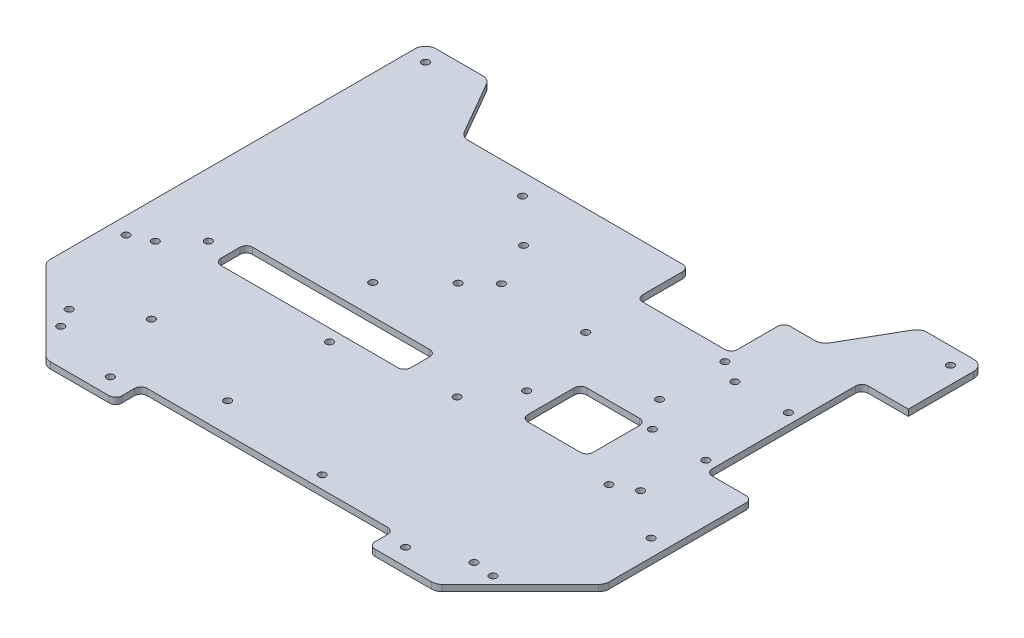
SolidWorks part; units mm, degrees
material "Acier non allié"
ref_plane "Front" through (0, 0, 0) normal (0, 0, 1) x (1, 0, 0)
ref_plane "Top" through (0, 0, 0) normal (0, 1, 0) x (1, 0, 0)
ref_plane "Right" through (0, 0, 0) normal (1, 0, 0) x (0, 0, -1)
sketch "Esquisse1" plane through (0, 0, 0) normal (0, 1, 0) x (1, 0, 0)
  line L0 (0, 0) -> (0, 190) construction
  line L1 (-92.5, 0) -> (92.5, 0)
  line L2 (92.5, 0) -> (132.5, 40)
  line L3 (132.5, 40) -> (132.5, 220)
  line L4 (132.5, 220) -> (102.5, 220)
  line L5 (102.5, 220) -> (85.1795, 190)
  line L6 (85.1795, 190) -> (-85.1795, 190)
  line L7 (-102.5, 220) -> (-85.1795, 190)
  line L8 (-132.5, 220) -> (-102.5, 220)
  line L9 (-132.5, 40) -> (-132.5, 220)
  line L10 (-92.5, 0) -> (-132.5, 40)
  dimension "D1" = 132.5
  dimension "D2" = 220
  dimension "D3" = 60
  dimension "D4" = 30
  dimension "D5" = 40
  dimension "D6" = 40
  dimension "D7" = 30
extrude "Boss.-Extru.1" add sketch "Esquisse1" along normal blind 3
fillet "Congé1" radius 5 10 edges at (92.5, 1.5, 0) (132.5, 1.5, -40) (132.5, 1.5, -220) (102.5, 1.5, -220) (85.1795, 1.5, -190) (-85.1795, 1.5, -190) (-102.5, 1.5, -220) (-132.5, 1.5, -220) (-92.5, 1.5, 0) (-132.5, 1.5, -40)
sketch "Esquisse2" plane through (0, 3, 0) normal (0, 1, 0) x (1, 0, 0)
  line L0 (0, 0) -> (0, 294.1173) construction
  line L2 (-90.4289, 0) -> (90.4289, 0) construction
  circle A0 centre (70, 8) radius 1
  circle A1 centre (124.5, 70) radius 1
  circle A2 centre (124.5, 212) radius 1
  circle A3 centre (-124.5, 212) radius 1
  circle A4 centre (-124.5, 70) radius 1
  circle A5 centre (-70, 8) radius 1
  dimension "D2" = 2
  dimension "D6" = 2
  dimension "D9" = 2
  dimension "D1" = 70
  dimension "D3" = 8
  dimension "D4" = 124.5
  dimension "D5" = 70
  dimension "D7" = 124.5
  dimension "D8" = 212
extrude "Enlèv. mat.-Extru.1" cut sketch "Esquisse2" against normal blind 3
hole_wizard "Dégagement M31" positions "Esquisse3" profile "Esquisse4" hole size "M3" standard "ISO" end condition through all
sketch "Esquisse3" plane through (0, 3, 0) normal (0, 1, 0) x (1, 0, 0)
  point P0 (70, 8)
  point P3 (-70, 8)
  point P6 (-124.5, 70)
  point P9 (-124.5, 212)
  point P12 (124.5, 212)
  point P15 (124.5, 70)
sketch "Esquisse4" plane through (70, 3, -8) normal (1, 0, 0) x (0, 0, 1)
  line L0 (0, 0) -> (0, 3)
  line L1 (0, 3) -> (1.7, 3)
  line L2 (1.7, 3) -> (1.7, 0)
  line L5 (1.7, 0) -> (0, 0)
  line L11 (0, -6.35) -> (0, 107.95) construction
  dimension "Diamètre du perçage jusqu'au prochain" = 3.4
  dimension "Profondeur du perçage jusqu'au prochain" = 3
sketch "Esquisse5" plane through (0, 3, 0) normal (0, 1, 0) x (1, 0, 0)
  line L0 (82.2927, 190) -> (-82.2927, 190) construction
  line L1 (67.5, 190) -> (22.5, 190)
  line L2 (67.5, 190) -> (67.5, 165)
  line L3 (67.5, 165) -> (22.5, 165)
  line L4 (22.5, 190) -> (22.5, 165)
  line L5 (132.5, 42.0711) -> (132.5, 215) construction
  line L6 (132.5, 184) -> (110.5, 184)
  line L7 (132.5, 184) -> (132.5, 110)
  line L8 (132.5, 110) -> (110.5, 110)
  line L9 (110.5, 184) -> (110.5, 110)
  line L10 (127.5, 220) -> (105.3868, 220) construction
  dimension "D1" = 25
  dimension "D2" = 65
  dimension "D3" = 110
  dimension "D4" = 36
  dimension "D5" = 110
  dimension "D6" = 22
extrude "Enlèv. mat.-Extru.2" cut sketch "Esquisse5" against normal through all
fillet "Congé2" radius 3 7 edges at (132.5, 1.5, -110) (110.5, 1.5, -110) (110.5, 1.5, -184) (67.5, 1.5, -190) (67.5, 1.5, -165) (22.5, 1.5, -165) (22.5, 1.5, -190)
sketch "Esquisse6" plane through (0, 3, 0) normal (0, 1, 0) x (1, 0, 0)
  line L0 (110.5, 144.5) -> (-167.6757, 144.5) construction
  line L1 (110.5, 181) -> (110.5, 113) construction
  line L2 (-90.4289, 0) -> (90.4289, 0) construction
  line L3 (110.5, 181) -> (110.5, 113) construction
  circle A0 centre (69.5, 160) radius 1
  circle A1 centre (-26, 160) radius 1
  circle A2 centre (-46.5, 180) radius 1
  circle A3 centre (69.5, 129) radius 1
  circle A4 centre (-26, 129) radius 1
  circle A5 centre (-46.5, 109) radius 1
  dimension "D4" = 2
  dimension "D6" = 2
  dimension "D10" = 2
  dimension "D1" = 144.5
  dimension "D2" = 41
  dimension "D3" = 15.5
  dimension "D5" = 136.5
  dimension "D7" = 15.5
  dimension "D8" = 35.5
  dimension "D9" = 157
extrude "Enlèv. mat.-Extru.3" cut sketch "Esquisse6" against normal through all
hole_wizard "Dégagement M32" positions "Esquisse7" profile "Esquisse8" hole size "M3" standard "ISO"
sketch "Esquisse7" plane through (0, 3, 0) normal (0, 1, 0) x (1, 0, 0)
  point P0 (-46.5, 109)
  point P3 (-26, 129)
  point P6 (-26, 160)
  point P9 (-46.5, 180)
  point P12 (69.5, 160)
  point P15 (69.5, 129)
sketch "Esquisse8" plane through (-46.5, 3, -109) normal (1, 0, 0) x (0, 0, 1)
  line L0 (0, 0) -> (0, 11.0215)
  line L1 (0, 11.0215) -> (1.7, 10)
  line L2 (1.7, 10) -> (1.7, 0)
  line L5 (1.7, 0) -> (0, 0)
  line L10 (0, 11.0215) -> (-1.7, 10) construction
  line L11 (0, -6.35) -> (0, 107.95) construction
  dimension "Diamètre du perçage" = 3.4
  dimension "Profondeur du perçage" = 10
  dimension "Angle de pointe" = 118
sketch "Esquisse9" plane through (0, 3, 0) normal (0, 1, 0) x (1, 0, 0)
  line L0 (132.5, 42.0711) -> (132.5, 107) construction
  line L1 (-90.4289, 0) -> (90.4289, 0) construction
  line L2 (-107.5, 26) -> (-32.37, 26) construction
  line L7 (20.5, 18) -> (20.5, 82) construction
  line L8 (25.5, 165) -> (64.5, 165) construction
  line L9 (24.5, 139) -> (-15.5, 139) construction
  line L10 (110.5, 181) -> (110.5, 113) construction
  line L11 (113.5, 110) -> (129.5, 110) construction
  line L13 (-32.37, 26) -> (-32.37, 74.3362) construction
  line L14 (-32.37, 74.3362) -> (-115, 74.3362) construction
  line L15 (-132.5, 215) -> (-132.5, 42.0711) construction
  circle A0 centre (105.5, 115) radius 1
  circle A3 centre (105.5, 154.12) radius 1
  circle A10 centre (20.5, 82) radius 1
  circle A11 centre (92.5, 82) radius 1
  circle A12 centre (20.5, 18) radius 1
  circle A13 centre (92.5, 18) radius 1
  circle A14 centre (-15.5, 139) radius 1
  circle A15 centre (24.5, 139) radius 1
  circle A16 centre (34.5, 101) radius 1
  circle A17 centre (80.1, 115) radius 1
  circle A18 centre (80.1, 154.12) radius 1
  circle A19 centre (-107.5, 26) radius 1.5
  circle A21 centre (-32.37, 26) radius 1.5
  circle A22 centre (-32.37, 74.3362) radius 1.5
  circle A23 centre (-115, 74.3362) radius 1.5
  circle A24 centre (-83.99, 41.44) radius 1.5
  dimension "D2" = 2
  dimension "D4" = 2
  dimension "D21" = 2
  dimension "D22" = 2
  dimension "D23" = 2
  dimension "D24" = 2
  dimension "D32" = 2
  dimension "D33" = 2
  dimension "D34" = 2
  dimension "D11" = 2
  dimension "D12" = 2
  dimension "D17" = 3
  dimension "D18" = 3
  dimension "D19" = 3
  dimension "D36" = 3
  dimension "D42" = 3
  dimension "D5" = 27
  dimension "25" = 27
  dimension "D10" = 39.12
  dimension "D25" = 72
  dimension "D26" = 72
  dimension "D27" = 64
  dimension "D28" = 64
  dimension "D30" = 18
  dimension "D31" = 18
  dimension "D37" = 40
  dimension "D39" = 10
  dimension "D7" = 5
  dimension "D8" = 25.4
  dimension "D9" = 25.4
  dimension "D40" = 39.12
  dimension "D38" = 76
  dimension "D6" = 38
  dimension "D35" = 26
  dimension "D14" = 40
  dimension "D13" = 75.13
  dimension "D15" = 82.63
  dimension "D16" = 48.3362
  dimension "D20" = 26
  dimension "D29" = 25
  dimension "D41" = 23.51
  dimension "D43" = 15.44
extrude "Enlèv. mat.-Extru.4" cut sketch "Esquisse9" against normal through all
hole_wizard "Dégagement M33" positions "Esquisse10" profile "Esquisse11" hole size "M3" standard "ISO"
sketch "Esquisse10" plane through (0, 3, 0) normal (0, 1, 0) x (1, 0, 0)
  point P3 (105.5, 115)
  point P9 (105.5, 154.12)
  point P14 (80.1, 154.12)
  point P17 (80.1, 115)
sketch "Esquisse11" plane through (105.5, 3, -115) normal (1, 0, 0) x (0, 0, 1)
  line L0 (0, 0) -> (0, 11.0215)
  line L1 (0, 11.0215) -> (1.7, 10)
  line L2 (1.7, 10) -> (1.7, 0)
  line L5 (1.7, 0) -> (0, 0)
  line L10 (0, 11.0215) -> (-1.7, 10) construction
  line L11 (0, -6.35) -> (0, 107.95) construction
  dimension "Diamètre du perçage" = 3.4
  dimension "Profondeur du perçage" = 10
  dimension "Angle de pointe" = 118
sketch "Esquisse12" plane through (0, 3, 0) normal (0, 1, 0) x (1, 0, 0)
  line L2 (-90.4289, 0) -> (90.4289, 0) construction
  line L3 (102.5, 17) -> (-102.5, 17) construction
  line L4 (102.5, 17) -> (102.5, 87) construction
  line L5 (102.5, 87) -> (-102.5, 87) construction
  line L6 (-102.5, 17) -> (-102.5, 87) construction
  line L7 (132.5, 42.0711) -> (132.5, 107) construction
  circle A4 centre (-102.5, 87) radius 1
  circle A5 centre (102.5, 87) radius 1
  circle A6 centre (102.5, 17) radius 1
  circle A7 centre (-102.5, 17) radius 1
  point P6 (102.5, 52)
  dimension "D5" = 2
  dimension "D6" = 2
  dimension "D7" = 2
  dimension "D8" = 2
  dimension "D1" = 70
  dimension "D2" = 205
  dimension "D3" = 17
  dimension "D4" = 30
extrude "Enlèv. mat.-Extru.5" cut sketch "Esquisse12" against normal through all and the other way through all
hole_wizard "Dégagement M34" positions "Esquisse13" profile "Esquisse14" hole size "M3" standard "ISO"
sketch "Esquisse13" plane through (0, 3, 0) normal (0, 1, 0) x (1, 0, 0)
  point P16 (20.5, 18)
  point P19 (92.5, 18)
  point P22 (20.5, 82)
  point P25 (92.5, 82)
  point P29 (34.5, 101)
  point P32 (24.5, 139)
  point P35 (-15.5, 139)
  point P38 (-115, 74.3362)
  point P41 (-32.37, 74.3362)
  point P44 (-107.5, 26)
  point P47 (-32.37, 26)
  point P50 (-83.99, 41.44)
sketch "Esquisse14" plane through (20.5, 3, -18) normal (1, 0, 0) x (0, 0, 1)
  line L0 (0, 0) -> (0, 11.0215)
  line L1 (0, 11.0215) -> (1.7, 10)
  line L2 (1.7, 10) -> (1.7, 0)
  line L5 (1.7, 0) -> (0, 0)
  line L10 (0, 11.0215) -> (-1.7, 10) construction
  line L11 (0, -6.35) -> (0, 107.95) construction
  dimension "Diamètre du perçage" = 3.4
  dimension "Profondeur du perçage" = 10
  dimension "Angle de pointe" = 118
hole_wizard "Dégagement M35" positions "Esquisse15" profile "Esquisse16" hole size "M3" standard "ISO"
sketch "Esquisse15" plane through (0, 3, 0) normal (0, 1, 0) x (1, 0, 0)
  point P0 (-102.5, 17)
  point P3 (-102.5, 87)
  point P6 (102.5, 87)
  point P9 (102.5, 17)
sketch "Esquisse16" plane through (-102.5, 3, -17) normal (1, 0, 0) x (0, 0, 1)
  line L0 (0, 0) -> (0, 11.0215)
  line L1 (0, 11.0215) -> (1.7, 10)
  line L2 (1.7, 10) -> (1.7, 0)
  line L5 (1.7, 0) -> (0, 0)
  line L10 (0, 11.0215) -> (-1.7, 10) construction
  line L11 (0, -6.35) -> (0, 107.95) construction
  dimension "Diamètre du perçage" = 3.4
  dimension "Profondeur du perçage" = 10
  dimension "Angle de pointe" = 118
sketch "Esquisse17" plane through (0, 3, 0) normal (0, 1, 0) x (1, 0, 0)
  line L0 (-90.4289, 0) -> (90.4289, 0) construction
  line L1 (-92.5, 95) -> (-2.5, 95)
  line L2 (-92.5, 95) -> (-92.5, 80)
  line L3 (-92.5, 80) -> (-2.5, 80)
  line L4 (-2.5, 95) -> (-2.5, 80)
  line L5 (-132.5, 215) -> (-132.5, 42.0711) construction
  line L6 (132.5, 42.0711) -> (132.5, 107) construction
  line L7 (44.5, 116.5) -> (75.5, 116.5)
  line L8 (44.5, 116.5) -> (44.5, 88.5)
  line L9 (44.5, 88.5) -> (75.5, 88.5)
  line L10 (75.5, 116.5) -> (75.5, 88.5)
  line L11 (82.2927, 190) -> (70.5, 190) construction
  line L13 (-59.5, 12) -> (60.5, 12)
  line L14 (-59.5, 12) -> (-59.5, 0)
  line L15 (-59.5, 0) -> (60.5, 0)
  line L16 (60.5, 12) -> (60.5, 0)
  dimension "D1" = 90
  dimension "D2" = 15
  dimension "D3" = 80
  dimension "D4" = 40
  dimension "D5" = 31
  dimension "D6" = 28
  dimension "D7" = 57
  dimension "D8" = 73.5
  dimension "D9" = 12
  dimension "D11" = 120
  dimension "D12" = 72
extrude "Enlèv. mat.-Extru.6" cut sketch "Esquisse17" against normal up to surface (3 mm away) up to face at (-102.5, 0, -15.3)
fillet "Congé3" radius 3 12 edges at (60.5, 1.5, 0) (60.5, 1.5, -12) (-59.5, 1.5, -12) (-59.5, 1.5, 0) (44.5, 1.5, -116.5) (75.5, 1.5, -116.5) (75.5, 1.5, -88.5) (44.5, 1.5, -88.5) (-92.5, 1.5, -80) (-2.5, 1.5, -80) (-2.5, 1.5, -95) (-92.5, 1.5, -95)
equation "\"WIDTH\"= 300mm'Total width of the robot"
equation "\"LENGTH\"= 220mm'Total length of the robot"
equation "\"CUT_DEPTH\"= 45mm'Depth of the cut on the edges of the plate"
equation "\"Plate_th\"= 3mm'Thickness of the plate"
equation "\"D1\"= \"Plate_th\""
equation "\"D5@Esquisse9\"=\"25@Esquisse9\""
